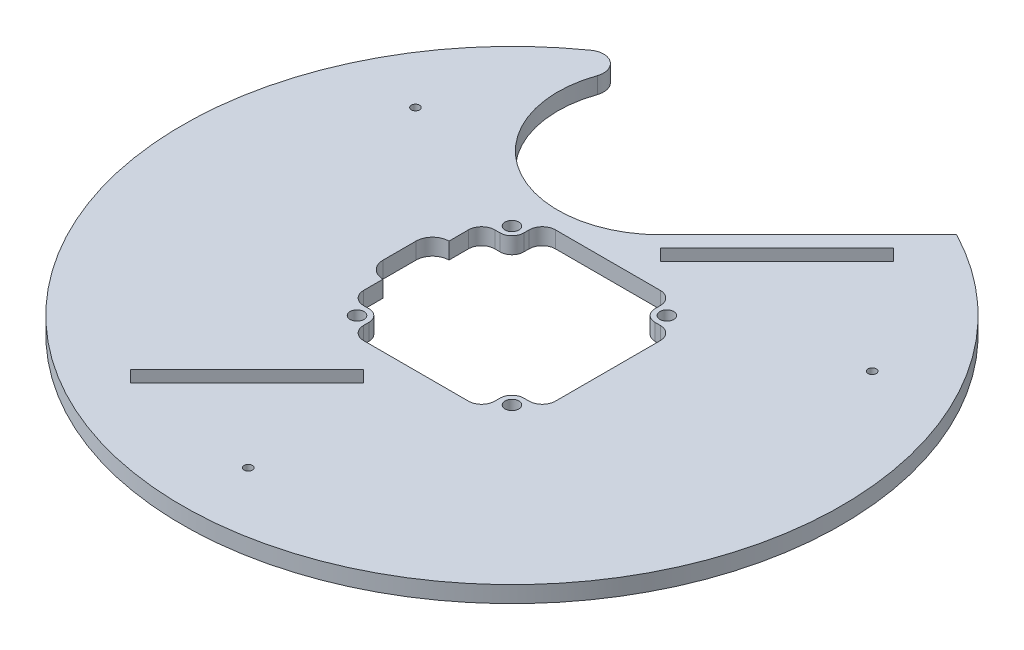
SolidWorks part; units mm, degrees
ref_plane "前基準面" through (0, 0, 0) normal (0, 0, 1) x (1, 0, 0)
ref_plane "上基準面" through (0, 0, 0) normal (0, 1, 0) x (1, 0, 0)
ref_plane "右基準面" through (0, 0, 0) normal (1, 0, 0) x (0, 0, -1)
sketch "草圖1" plane through (0, 0, 0) normal (0, 1, 0) x (1, 0, 0)
  line L2 (-99.6974, -7.7735) -> (17.2836, 109.2075) construction
  line L3 (8.3612, 36.6455) -> (43.7166, 72.0009)
  line L4 (-28.5, 28.5) -> (28.5, 28.5) construction
  line L5 (-28.5, 28.5) -> (-28.5, -28.5) construction
  line L6 (-28.5, -28.5) -> (28.5, -28.5) construction
  line L7 (28.5, 28.5) -> (28.5, -28.5) construction
  line L8 (8.3612, 36.6455) -> (4.8257, 40.181)
  line L9 (-18.8989, 23.5) -> (-18.8989, 25.1) construction
  line L10 (-25.1, 18.8989) -> (-23.5, 18.8989) construction
  line L11 (-18.8989, 23.5) -> (-18.8989, 25.1) construction
  line L12 (-25.1, 18.8989) -> (-23.5, 18.8989) construction
  line L13 (23.5, 18.8989) -> (25.1, 18.8989) construction
  line L14 (18.8989, 25.1) -> (18.8989, 23.5) construction
  line L15 (18.8989, -23.5) -> (18.8989, -25.1) construction
  line L16 (25.1, -18.8989) -> (23.5, -18.8989) construction
  line L17 (-23.5, -18.8989) -> (-25.1, -18.8989) construction
  line L18 (-18.8989, -25.1) -> (-18.8989, -23.5) construction
  line L19 (-15.8989, 28.1) -> (15.8989, 28.1) construction
  line L20 (28.1, 15.8989) -> (28.1, -15.8989) construction
  line L21 (-15.8989, -28.1) -> (15.8989, -28.1) construction
  line L22 (-28.1, 15.8989) -> (-28.1, -15.8989) construction
  line L23 (-19.8989, 23.5) -> (-19.8989, 25.1)
  line L24 (-15.8989, 29.1) -> (15.8989, 29.1)
  line L25 (19.8989, 25.1) -> (19.8989, 23.5)
  line L26 (23.5, 19.8989) -> (25.1, 19.8989)
  line L27 (29.1, 15.8989) -> (29.1, -15.8989)
  line L28 (25.1, -19.8989) -> (23.5, -19.8989)
  line L29 (19.8989, -23.5) -> (19.8989, -25.1)
  line L30 (-15.8989, -29.1) -> (15.8989, -29.1)
  line L31 (-19.8989, -25.1) -> (-19.8989, -23.5)
  line L32 (-23.5, -19.8989) -> (-25.1, -19.8989)
  line L33 (-29.1, 15.8989) -> (-29.1, -15.8989)
  line L34 (-25.1, 19.8989) -> (-23.5, 19.8989)
  line L35 (43.7166, 72.0009) -> (40.181, 75.5364)
  line L36 (40.181, 75.5364) -> (4.8257, 40.181)
  line L37 (40.181, 75.5364) -> (50.7877, 86.143) construction
  line L38 (-43.7166, -72.0009) -> (-40.181, -75.5364)
  line L39 (1.2902, 43.7166) -> (46.2405, 88.6669)
  line L40 (-8.3612, -36.6455) -> (-43.7166, -72.0009)
  line L41 (-40.181, -75.5364) -> (-4.8257, -40.181)
  line L42 (-8.3612, -36.6455) -> (-4.8257, -40.181)
  arc A20 (-57.6766, 81.6909) -> (46.2405, 88.6669) centre (0, 0) ccw
  circle A24 centre (0, 0) radius 20
  arc A27 (-15.8989, 28.1) -> (-18.8989, 25.1) centre (-15.8989, 25.1) ccw construction
  arc A28 (-25.1, 18.8989) -> (-28.1, 15.8989) centre (-25.1, 15.8989) ccw construction
  arc A29 (-23.5, 18.8989) -> (-18.8989, 23.5) centre (-23.5, 23.5) ccw construction
  arc A30 (-15.8989, 28.1) -> (-18.8989, 25.1) centre (-15.8989, 25.1) ccw construction
  arc A31 (-25.1, 18.8989) -> (-28.1, 15.8989) centre (-25.1, 15.8989) ccw construction
  arc A32 (-23.5, 18.8989) -> (-18.8989, 23.5) centre (-23.5, 23.5) ccw construction
  arc A33 (28.1, 15.8989) -> (25.1, 18.8989) centre (25.1, 15.8989) ccw construction
  arc A34 (18.8989, 25.1) -> (15.8989, 28.1) centre (15.8989, 25.1) ccw construction
  arc A35 (18.8989, 23.5) -> (23.5, 18.8989) centre (23.5, 23.5) ccw construction
  arc A36 (15.8989, -28.1) -> (18.8989, -25.1) centre (15.8989, -25.1) ccw construction
  arc A37 (25.1, -18.8989) -> (28.1, -15.8989) centre (25.1, -15.8989) ccw construction
  arc A38 (23.5, -18.8989) -> (18.8989, -23.5) centre (23.5, -23.5) ccw construction
  arc A39 (-28.1, -15.8989) -> (-25.1, -18.8989) centre (-25.1, -15.8989) ccw construction
  arc A40 (-18.8989, -25.1) -> (-15.8989, -28.1) centre (-15.8989, -25.1) ccw construction
  arc A41 (-18.8989, -23.5) -> (-23.5, -18.8989) centre (-23.5, -23.5) ccw construction
  arc A42 (-23.5, 19.8989) -> (-19.8989, 23.5) centre (-23.5, 23.5) ccw
  arc A43 (-15.8989, 29.1) -> (-19.8989, 25.1) centre (-15.8989, 25.1) ccw
  arc A44 (19.8989, 25.1) -> (15.8989, 29.1) centre (15.8989, 25.1) ccw
  arc A45 (19.8989, 23.5) -> (23.5, 19.8989) centre (23.5, 23.5) ccw
  arc A46 (29.1, 15.8989) -> (25.1, 19.8989) centre (25.1, 15.8989) ccw
  arc A47 (25.1, -19.8989) -> (29.1, -15.8989) centre (25.1, -15.8989) ccw
  arc A48 (23.5, -19.8989) -> (19.8989, -23.5) centre (23.5, -23.5) ccw
  arc A49 (15.8989, -29.1) -> (19.8989, -25.1) centre (15.8989, -25.1) ccw
  arc A50 (-19.8989, -25.1) -> (-15.8989, -29.1) centre (-15.8989, -25.1) ccw
  arc A51 (-19.8989, -23.5) -> (-23.5, -19.8989) centre (-23.5, -23.5) ccw
  arc A52 (-29.1, -15.8989) -> (-25.1, -19.8989) centre (-25.1, -15.8989) ccw
  arc A53 (-25.1, 19.8989) -> (-29.1, 15.8989) centre (-25.1, 15.8989) ccw
  circle A54 centre (0, 0) radius 65 construction
  circle A55 centre (-60.6477, -23.3851) radius 35 construction
  circle A56 centre (83.3354, 168.1883) radius 35 construction
  arc A58 (-50.072, 75.959) -> (1.2902, 43.7166) centre (-20.7041, 65.7109) ccw
  arc A59 (-57.6766, 81.6909) -> (-50.072, 75.959) centre (-54.7928, 77.6064) cw
  point P16 (0, 28.5)
  point P18 (-28.5, 0)
  dimension "D1" = 4
  dimension "D2" = 200
  dimension "D3" = 130
  dimension "D4" = 40
  dimension "D6" = 1
  dimension "D8" = 45
  dimension "D11" = 15
  dimension "D12" = 70
  dimension "D13" = 5
  dimension "D15" = 2
  dimension "D5" = 57
  dimension "D9" = 5
  dimension "D10" = 50
  dimension "D7" = 45
  dimension "D14" = 5
extrude "填料-伸長1" add sketch "草圖1" against normal blind 5 contours A20 A53 L34 A42 L23 A43 L24 A44 L25 A45 L26 A46 L27 A47 L28 A48 L29 A49 L30 A50 L31 A51 L32 A52 L33 region at (25.7095, 0, -64.2476)
sketch "草圖2" plane through (0, 0, 0) normal (0, 1, 0) x (1, 0, 0)
  line L1 (-23.5, 23.5) -> (23.5, 23.5)
  line L2 (-23.5, 23.5) -> (-23.5, -23.5)
  line L3 (-23.5, -23.5) -> (23.5, -23.5)
  line L4 (23.5, 23.5) -> (23.5, -23.5)
  point P9 (23.5, 0)
  point P15 (0, 23.5)
  dimension "D1" = 47
sketch "草圖5" plane through (0, 0, 0) normal (0, 1, 0) x (1, 0, 0)
  line L0 (-29.1, -5) -> (-29.1, 5) construction
  line L2 (-34.1, -5) -> (-34.1, 5)
  line L3 (-24.1, -5) -> (-24.1, 5)
  line L4 (-29.1, 15.8989) -> (-29.1, -15.8989) construction
  arc A0 (-34.1, -5) -> (-24.1, -5) centre (-29.1, -5) ccw
  arc A1 (-24.1, 5) -> (-34.1, 5) centre (-29.1, 5) ccw
  point P2 (-21.2999, 9.5316)
  point P3 (-29.1, 0)
  point P4 (-29.1, 0)
  point P9 (0, 0)
  dimension "D1" = 10
  dimension "D2" = 10
extrude "除料-伸長1" cut sketch "草圖5" against normal through all both and the other way through all contours L2 A1 L3 A0
hole_wizard "M5  螺絲攻的螺孔鑽1" positions "草圖3" profile "草圖4" hole size "M5" standard "ISO" end condition through all
sketch "草圖3" plane through (0, 0, 0) normal (0, 1, 0) x (1, 0, 0)
  point P13 (23.5, 23.5)
  point P16 (23.5, -23.5)
  point P19 (-23.5, -23.5)
  point P22 (-23.5, 23.5)
sketch "草圖4" plane through (23.5, 0, -23.5) normal (1, 0, 0) x (0, 0, 1)
  line L0 (0, 0) -> (0, 5)
  line L1 (0, 5) -> (2.1, 5)
  line L2 (2.1, 5) -> (2.1, 0)
  line L5 (2.1, 0) -> (0, 0)
  line L11 (0, -6.35) -> (0, 107.95) construction
  dimension "貫穿孔直徑" = 4.2
  dimension "貫穿孔深度" = 5
sketch "草圖6" plane through (0, 0, 0) normal (0, 1, 0) x (1, 0, 0)
  line L0 (0, 0) -> (0, -80)
  line L1 (0, 0) -> (-69.282, 40)
  line L2 (0, 0) -> (69.282, 40)
  dimension "D1" = 3
  dimension "D2" = 80
hole_wizard "M3  螺絲攻的螺孔鑽1" positions "草圖7" profile "草圖8" hole size "M3" standard "ISO" end condition through all
sketch "草圖7" plane through (0, 0, 0) normal (0, 1, 0) x (1, 0, 0)
  point P0 (-69.282, 40)
  point P3 (0, -80)
  point P6 (69.282, 40)
sketch "草圖8" plane through (-69.282, 0, -40) normal (1, 0, 0) x (0, 0, 1)
  line L0 (0, 0) -> (0, 5)
  line L1 (0, 5) -> (1.25, 5)
  line L2 (1.25, 5) -> (1.25, 0)
  line L5 (1.25, 0) -> (0, 0)
  line L11 (0, -6.35) -> (0, 107.95) construction
  dimension "貫穿孔直徑" = 2.5
  dimension "貫穿孔深度" = 5
